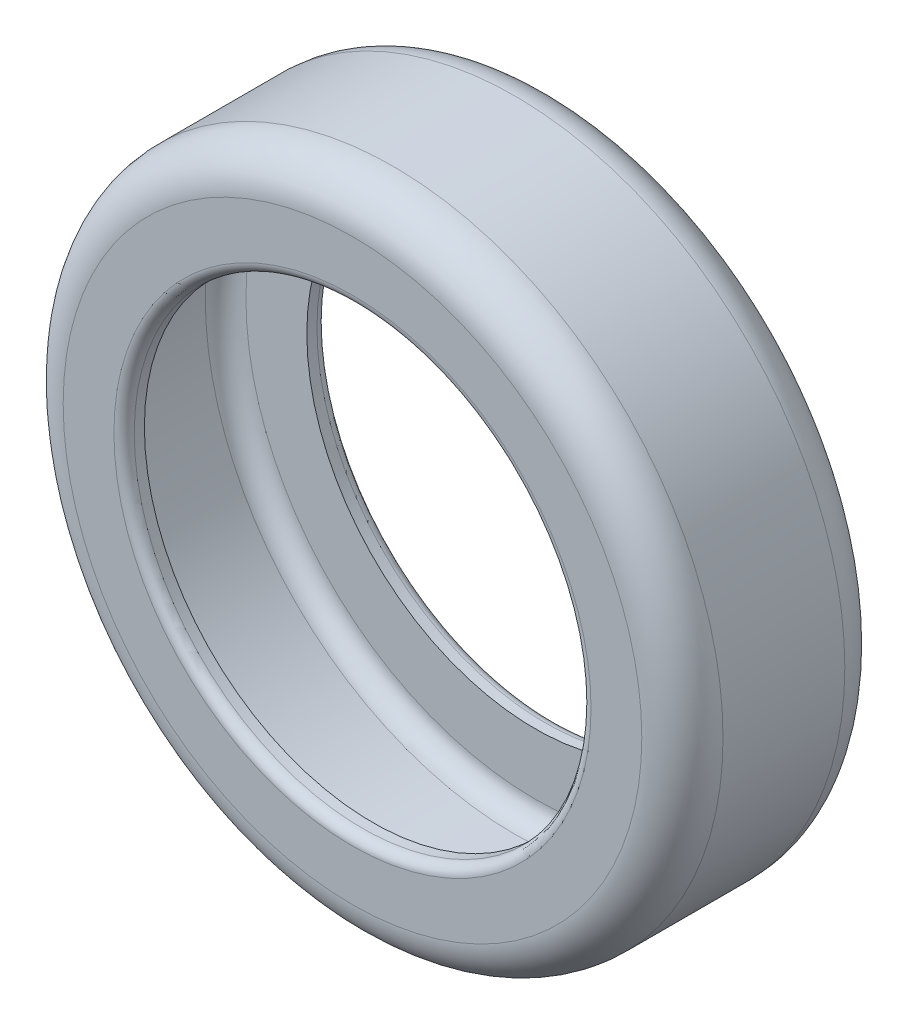
SolidWorks part; units mm, degrees
ref_plane "Front Plane" through (0, 0, 0) normal (0, 0, 1) x (1, 0, 0)
ref_plane "Top Plane" through (0, 0, 0) normal (0, 1, 0) x (1, 0, 0)
ref_plane "Right Plane" through (0, 0, 0) normal (1, 0, 0) x (0, 0, -1)
sketch "Sketch1" plane through (0, 0, 0) normal (0, 0, 1) x (1, 0, 0)
  circle A0 centre (0, 0) radius 22.5
  dimension "D1" = 45
extrude "Extrude-Thin1" add sketch "Sketch1" along normal blind 20 thin thin type one direction wall 10
fillet "Fillet1" radius 4 2 edges at (32.5, 0, 0) (32.5, 0, 20)
fillet "Fillet2" radius 1 2 edges at (22.5, 0, 20) (22.5, 0, 0)
shell "Shell1" thickness 2 removed face at (22.5, 0, 19)
